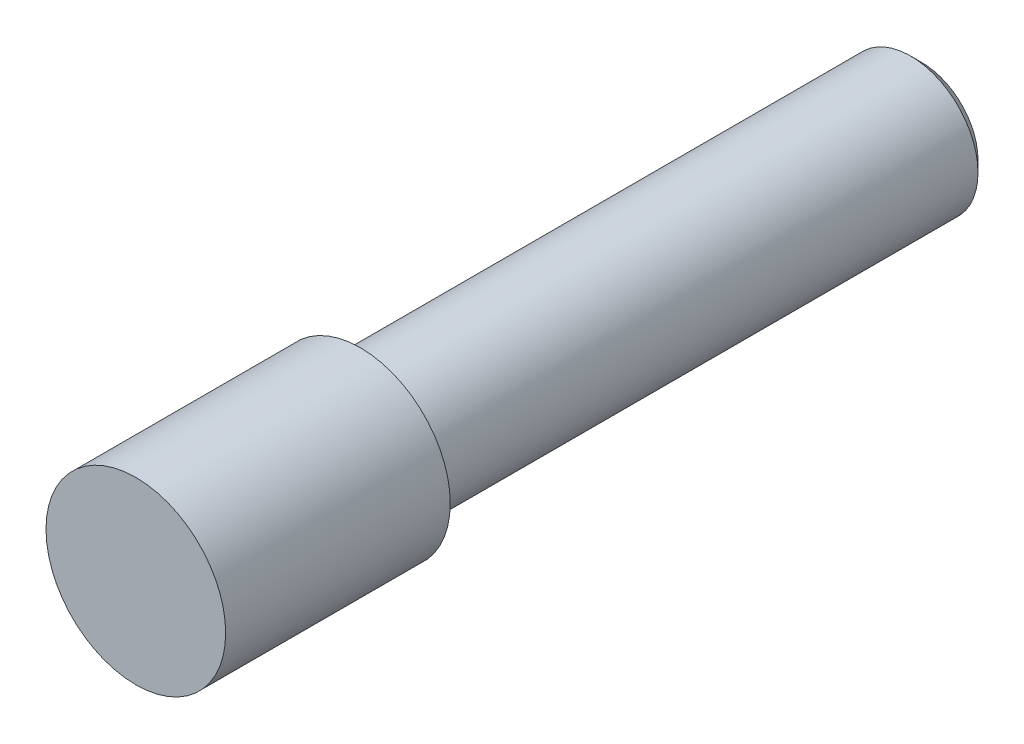
SolidWorks part; units mm, degrees
ref_plane "Front" through (0, 0, 0) normal (0, 0, 1) x (1, 0, 0)
ref_plane "Top" through (0, 0, 0) normal (0, 1, 0) x (1, 0, 0)
ref_plane "Right" through (0, 0, 0) normal (1, 0, 0) x (0, 0, -1)
sketch "Esquisse1" plane through (0, 0, 0) normal (0, 0, 1) x (1, 0, 0)
  circle A0 centre (0, 0) radius 3
  dimension "D1" = 6
extrude "Boss.-Extru.1" add sketch "Esquisse1" along normal blind 25
chamfer "Chanfrein1" distance 0.5 angle 45 1 edges at (3, 0, 0)
sketch "Esquisse2" plane through (0, 0, 25) normal (0, 0, 1) x (1, 0, 0)
  circle A0 centre (0, 0) radius 4
  dimension "D1" = 8
extrude "Boss.-Extru.2" add sketch "Esquisse2" along normal blind 10
